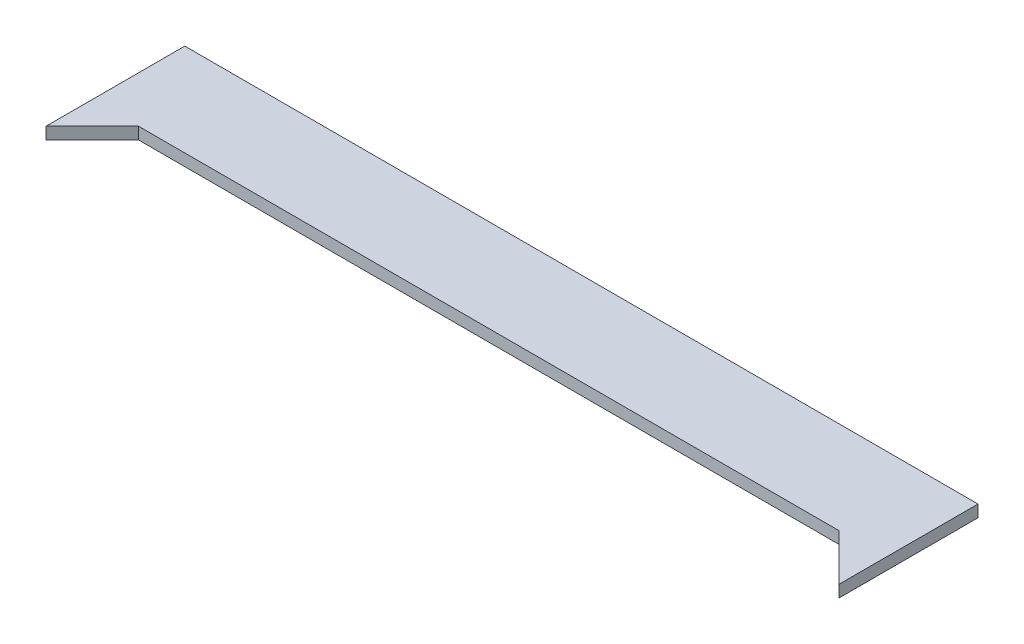
SolidWorks part; units mm, degrees
material "Wrought Stainless Steel"
ref_plane "Front Plane" through (0, 0, 0) normal (0, 0, 1) x (1, 0, 0)
ref_plane "Top Plane" through (0, 0, 0) normal (0, 1, 0) x (1, 0, 0)
ref_plane "Right Plane" through (0, 0, 0) normal (1, 0, 0) x (0, 0, -1)
sketch "Sketch1" plane through (0, 0, 0) normal (0, 1, 0) x (1, 0, 0)
  line L0 (0, -1000) -> (0, 49000) construction
  line L1 (-1000, 0) -> (-200, 0) construction
  line L2 (-1180.5995, 23.33) -> (48819.4005, 23.33) construction
  line L4 (-200, 0) -> (-200, 70)
  line L5 (-200, 70) -> (200, 70)
  line L6 (200, 0) -> (200, 70)
  line L7 (200, 0) -> (176.67, 23.33)
  line L8 (-176.67, 23.33) -> (176.67, 23.33)
  line L9 (-200, 0) -> (-176.67, 23.33)
  line L10 (200, 0) -> (49000, 0) construction
  point P16 (0, 23.33)
  dimension "D2" = 70
  dimension "D3" = 400
  dimension "D4" = 46.67
  dimension "D5" = 45
extrude "Boss-Extrude1" add sketch "Sketch1" along normal blind 6
